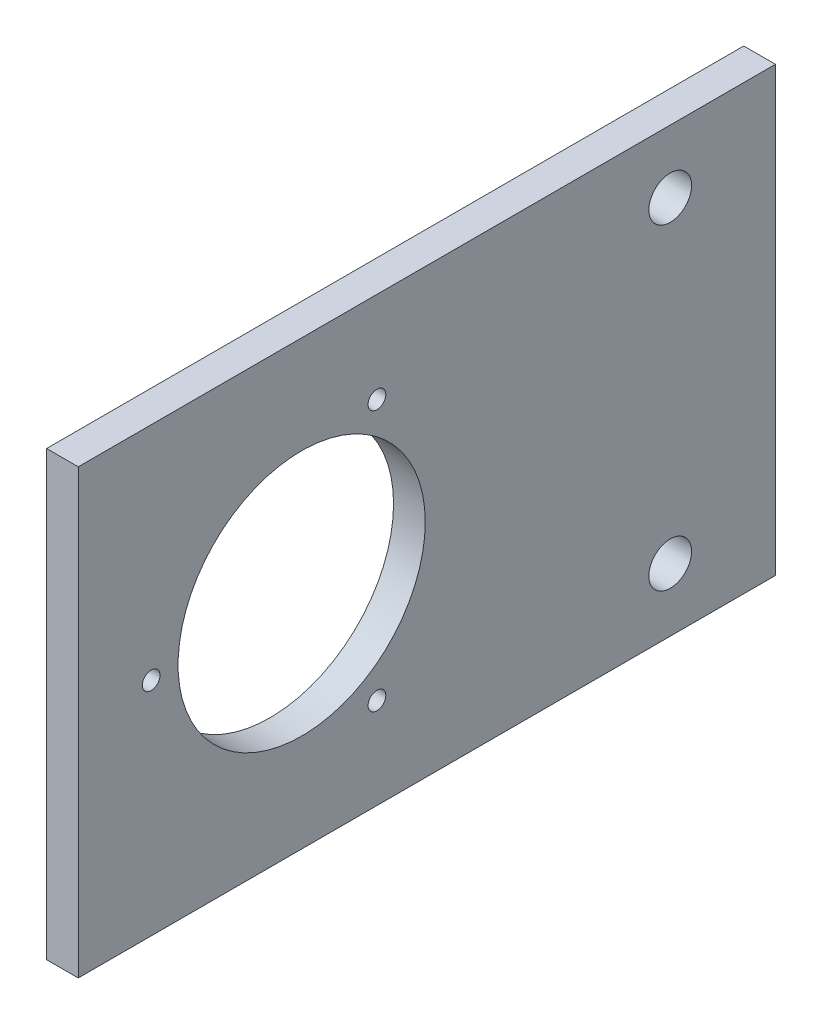
SolidWorks part; units mm, degrees
ref_plane "Front Plane" through (0, 0, 0) normal (1, 0, 0) x (0, 1, 0)
ref_plane "Top Plane" through (0, 0, 0) normal (0, 0, 1) x (0, 1, 0)
ref_plane "Right Plane" through (0, 0, 0) normal (0, 1, 0) x (-1, 0, 0)
sketch "Sketch1" plane through (0, 0, 0) normal (1, 0, 0) x (0, 1, 0)
  line L0 (-34.925, 19.75) -> (34.925, 19.75) construction
  line L1 (-34.925, -55) -> (34.925, -55)
  line L2 (-34.925, -55) -> (-34.925, 55)
  line L3 (-34.925, 55) -> (34.925, 55)
  line L4 (34.925, -55) -> (34.925, 55)
  line L5 (-34.925, -55) -> (34.925, 55) construction
  line L6 (-34.925, 55) -> (34.925, -55) construction
  line L7 (0, 55) -> (0, -55) construction
  line L8 (-34.925, -38.4) -> (34.925, -38.4) construction
  line L9 (0, 19.75) -> (0, 43.5) construction
  line L10 (20.5681, 7.875) -> (0, 19.75) construction
  line L11 (0, 19.75) -> (-20.5681, 7.875) construction
  circle A5 centre (0, 19.75) radius 19.5
  circle A6 centre (-25, -38.4) radius 3.3731
  circle A7 centre (25, -38.4) radius 3.3731
  circle A8 centre (-20.5681, 7.875) radius 1.4
  circle A9 centre (20.5681, 7.875) radius 1.4
  circle A10 centre (0, 43.5) radius 1.4
  point P0 (0, 0)
  dimension "D5" = 2.8
  dimension "D4" = 23.75
  dimension "D6" = 120
  dimension "D8" = 39
  dimension "D10" = 6.7462
  dimension "D1" = 110
  dimension "D2" = 69.85
  dimension "D3" = 74.75
  dimension "D7" = 120
  dimension "D9" = 16.6
  dimension "D11" = 25
extrude "Boss-Extrude1" add sketch "Sketch1" along normal blind 5
